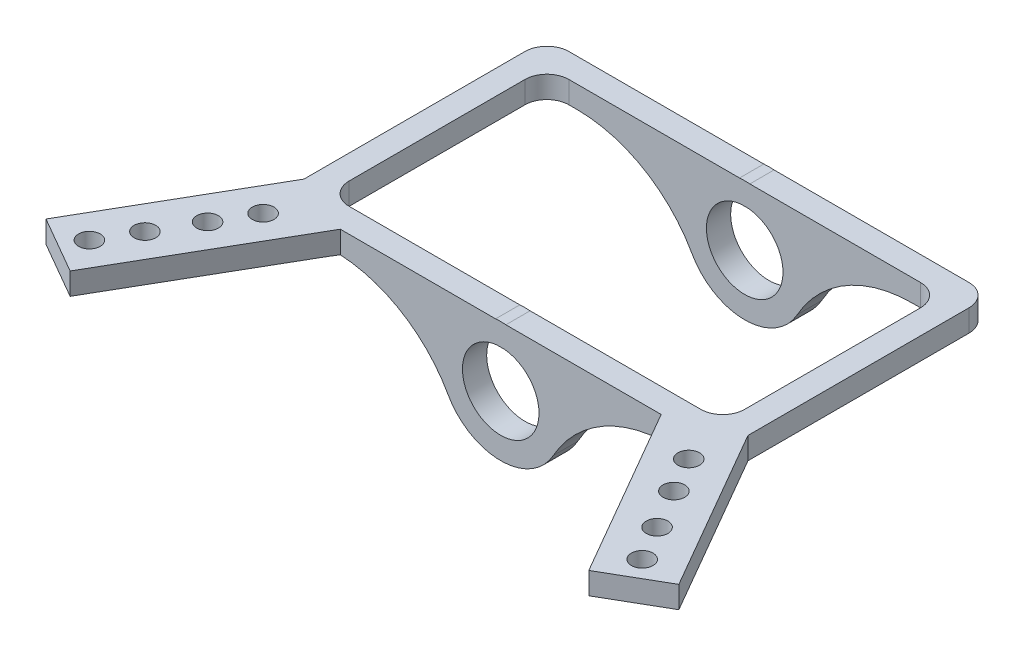
SolidWorks part; units mm, degrees
ref_plane "Front Plane" through (0, 0, 0) normal (0, 0, 1) x (1, 0, 0)
ref_plane "Top Plane" through (0, 0, 0) normal (0, 1, 0) x (1, 0, 0)
ref_plane "Right Plane" through (0, 0, 0) normal (1, 0, 0) x (0, 0, -1)
sketch "Sketch2" plane through (0, 0, 0) normal (0, 1, 0) x (1, 0, 0)
  line L0 (-64.5613, 62.0343) -> (-64.5613, -8.1773)
  line L1 (63.7387, 62.0343) -> (63.7387, -8.1773)
  line L2 (63.7387, -8.1773) -> (91.0224, -55.434)
  line L4 (-57.5613, -8.4657) -> (56.7387, -8.4657)
  line L5 (-64.5613, -8.1773) -> (-91.845, -55.434)
  line L6 (-46.7722, -15.4657) -> (-75.3472, -64.959)
  line L7 (-46.7722, -15.4657) -> (45.9496, -15.4657)
  line L8 (45.9496, -15.4657) -> (74.5246, -64.959)
  line L9 (-91.845, -55.434) -> (-75.3472, -64.959)
  line L10 (74.5246, -64.959) -> (91.0224, -55.434)
  line L12 (-64.5613, 62.0343) -> (63.7387, 62.0343)
  line L14 (-57.5613, 55.0343) -> (-57.5613, -8.4657)
  line L15 (-57.5613, 55.0343) -> (56.7387, 55.0343)
  line L16 (56.7387, 55.0343) -> (56.7387, -8.4657)
  point P1 (-0.4113, -15.4657)
  point P2 (-0.4113, -8.4657)
  point P4 (22.6666, 63.7548)
  dimension "D1" = 7
  dimension "D2" = 19.05
  dimension "D3" = 7
  dimension "D4" = 7
  dimension "D8" = 19.05
  dimension "D7" = 7
  dimension "D9" = 114.3
  dimension "D10" = 57.15
  dimension "D5" = 120
  dimension "D6" = 120
  dimension "D11" = 63.5
extrude "Boss-Extrude1" add sketch "Sketch2" along normal blind 6.35
sketch "Sketch3" plane through (0, 6.35, 0) normal (0, 1, 0) x (1, 0, 0)
  line L0 (-91.845, -55.434) -> (-75.3472, -64.959) construction
  line L1 (-75.3472, -64.959) -> (-46.7722, -15.4657) construction
  line L2 (-0.4113, -8.4657) -> (-0.4113, -15.4657) construction
  line L3 (56.7387, -8.4657) -> (-57.5613, -8.4657) construction
  line L4 (-46.7722, -15.4657) -> (45.9496, -15.4657) construction
  circle A0 centre (-67.7836, -32.8085) radius 3.125
  circle A1 centre (-61.9086, -22.6327) radius 3.125
  circle A2 centre (-74.4086, -44.2833) radius 3.125
  circle A3 centre (-80.2836, -54.4591) radius 3.125
  circle A4 centre (79.461, -54.4591) radius 3.125
  circle A5 centre (73.586, -44.2833) radius 3.125
  circle A6 centre (61.086, -22.6327) radius 3.125
  circle A7 centre (66.961, -32.8085) radius 3.125
  dimension "D3" = 9.525
  dimension "D4" = 11.75
  dimension "D6" = 9.525
  dimension "D7" = 13.25
  dimension "D8" = 11.75
  dimension "D9" = 6.25
  dimension "D1" = 6.625
  dimension "D2" = 9.525
  dimension "D5" = 9.525
extrude "Cut-Extrude1" cut sketch "Sketch3" against normal up to next
sketch "Sketch5" plane through (0, 0, -62.0343) normal (0, 0, -1) x (-1, 0, 0)
  line L0 (-63.7387, 0) -> (64.5613, 0) construction
  line L4 (57.5613, 6.35) -> (57.5613, 0) construction
  circle A0 centre (0.4113, -11) radius 11.0635
  circle A1 centre (0.4113, -11) radius 17.4135
  dimension "D1" = 11
  dimension "D4" = 22.127
  dimension "D3" = 57.15
  dimension "D2" = 6.35
extrude "Boss-Extrude7" add sketch "Sketch5" against normal up to surface (77.5 mm away) up to face at (-0.4113, 3.175, 15.4657)
fillet "Fillet1" radius 38.1 4 edges at (-13.9106, 0, -58.5343) (13.0879, 0, -58.5343) (-13.9106, 0, 11.9657) (13.0879, 0, 11.9657)
sketch "Sketch6" plane through (0, 6.35, 0) normal (0, 1, 0) x (1, 0, 0)
  line L12 (-57.5613, 55.0343) -> (56.7387, 55.0343)
  line L13 (-57.5613, 55.0343) -> (-57.5613, -8.4657)
  line L14 (-57.5613, -8.4657) -> (56.7387, -8.4657)
  line L15 (56.7387, 55.0343) -> (56.7387, -8.4657)
extrude "Cut-Extrude2" cut sketch "Sketch6" against normal through all both and the other way through all
fillet "Fillet2" radius 6.35 6 edges at (-64.5613, 3.175, -62.0343) (-57.5613, 3.175, 8.4657) (-57.5613, 3.175, -55.0343) (63.7387, 3.175, -62.0343) (56.7387, 3.175, -55.0343) (56.7387, 3.175, 8.4657)
